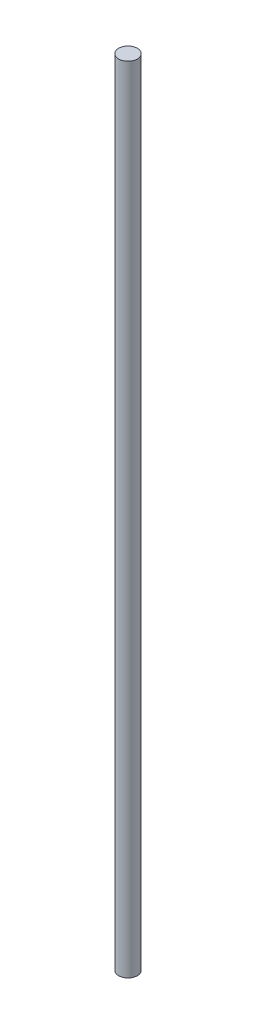
SolidWorks part; units mm, degrees
material "Plain Carbon Steel"
ref_plane "Front Plane" through (0, 0, 0) normal (0, 0, 1) x (1, 0, 0)
ref_plane "Top Plane" through (0, 0, 0) normal (0, 1, 0) x (1, 0, 0)
ref_plane "Right Plane" through (0, 0, 0) normal (1, 0, 0) x (0, 0, -1)
sketch "Sketch1" plane through (0, 0, 0) normal (0, 1, 0) x (1, 0, 0)
  circle A0 centre (0, 0) radius 4
extrude "Boss-Extrude1" add sketch "Sketch1" along normal blind 340
